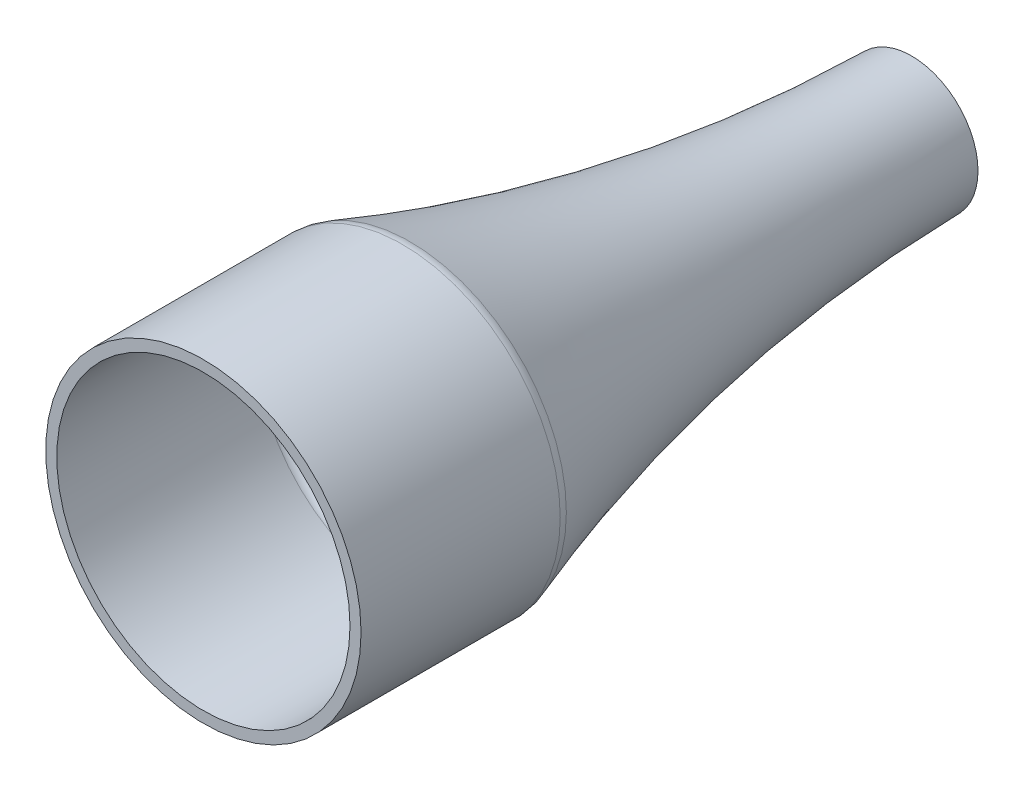
SolidWorks part; units mm, degrees
ref_plane "Plano frontal" through (0, 0, 0) normal (0, 0, 1) x (1, 0, 0)
ref_plane "Plano superior" through (0, 0, 0) normal (0, 1, 0) x (1, 0, 0)
ref_plane "Plano direito" through (0, 0, 0) normal (1, 0, 0) x (0, 0, -1)
sketch "Esboço1" plane through (0, 0, 0) normal (0, 0, 1) x (1, 0, 0)
  circle A0 centre (0, 0) radius 3
  dimension "D1" = 6
ref_plane "Plano1" through (0, 0, 32) normal (0, 0, 1) x (1, 0, 0)
sketch "Esboço2" plane through (0, 0, 32) normal (0, 0, 1) x (1, 0, 0)
  circle A0 centre (0, 0) radius 7.125
  dimension "D1" = 14.25
extrude "Ressalto-extrusão1" add sketch "Esboço1" along normal blind 32 contours A0
extrude "Ressalto-extrusão2" add sketch "Esboço2" against normal blind 10 contours A0
fillet "Filete19" radius 1 1 edges at (7.125, 0, 22)
shell "Casca1" thickness 0.5 removed face at (7.125, 0, 32) removed face at (3, 0, 0)
fillet "Filete22" radius 71 1 edges at (3, 0, 22)
equation "\"0.5.00mm\"=1"
